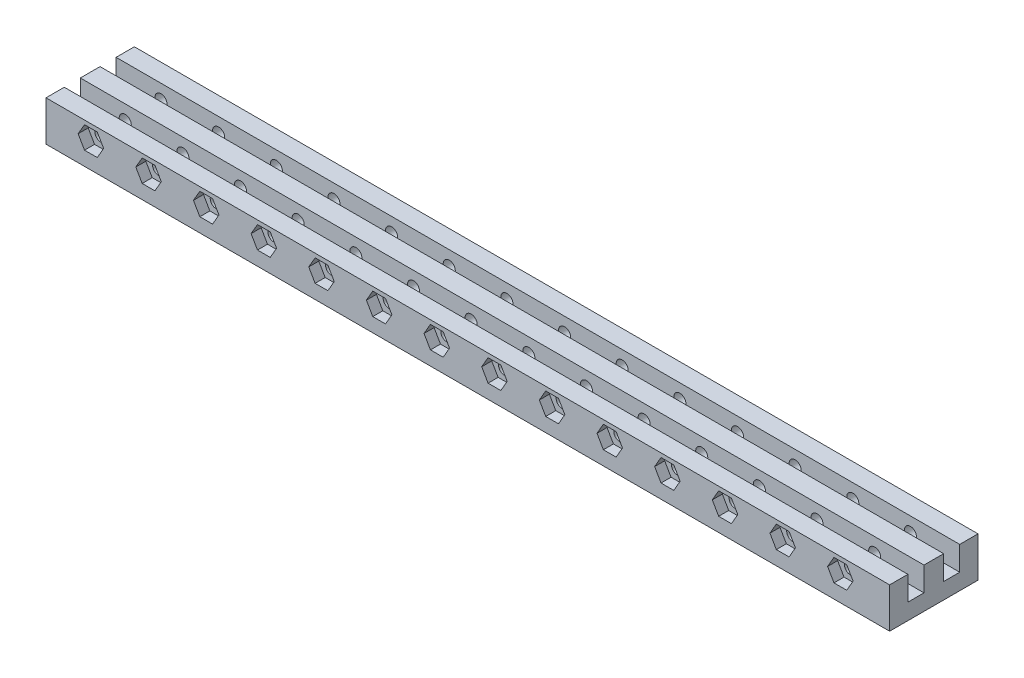
SolidWorks part; units mm, degrees
ref_plane "Front Plane" through (0, 0, 0) normal (0, 0, 1) x (1, 0, 0)
ref_plane "Top Plane" through (0, 0, 0) normal (0, 1, 0) x (1, 0, 0)
ref_plane "Right Plane" through (0, 0, 0) normal (1, 0, 0) x (0, 0, -1)
sketch "Sketch1" plane through (0, 0, 0) normal (0, 1, 0) x (1, 0, 0)
  line L1 (105, -11) -> (-105, -11)
  line L2 (105, -11) -> (105, 11)
  line L3 (105, 11) -> (-105, 11)
  line L4 (-105, -11) -> (-105, 11)
  line L5 (0, 11) -> (0, -11) construction
  line L6 (105, 0) -> (-105, 0) construction
  point P0 (0, 0)
  point P4 (0, 0)
  dimension "D1" = 210
  dimension "D2" = 22
extrude "Boss-Extrude1" add sketch "Sketch1" along normal blind 10
sketch "Sketch2" plane through (0, 10, 0) normal (0, 1, 0) x (1, 0, 0)
  line L0 (-105, 11) -> (-105, -11) construction
  line L1 (-105, -2.4504) -> (105, -2.4504)
  line L2 (-105, -2.4504) -> (-105, -6.4504)
  line L3 (-105, -6.4504) -> (105, -6.4504)
  line L4 (105, -2.4504) -> (105, -6.4504)
  line L5 (105, -11) -> (105, 11) construction
  line L6 (-105, 0) -> (108.3852, 0) construction
  line L7 (-105, -11) -> (105, -11) construction
  line L8 (105, 2.4504) -> (105, 6.4504)
  line L9 (-105, 2.4504) -> (-105, 6.4504)
  line L10 (-105, 2.4504) -> (105, 2.4504)
  line L11 (-105, 6.4504) -> (105, 6.4504)
  dimension "D1" = 4
extrude "Cut-Extrude1" cut sketch "Sketch2" against normal blind 6
sketch "Sketch3" plane through (0, 0, 11) normal (0, 0, 1) x (1, 0, 0)
  line L6 (-97, 6.25) -> (-90.6491, 6.25) construction
  line L7 (-105, 10) -> (105, 10) construction
  line L8 (-90.6491, 6.25) -> (-92.2369, 9)
  line L9 (-92.2369, 9) -> (-95.4123, 9)
  line L10 (-95.4123, 9) -> (-97, 6.25)
  line L11 (-97, 6.25) -> (-95.4123, 3.5)
  line L12 (-95.4123, 3.5) -> (-92.2369, 3.5)
  line L13 (-92.2369, 3.5) -> (-90.6491, 6.25)
  line L14 (-105, 10) -> (-105, 0) construction
  line L15 (-86.6491, 10) -> (-86.6491, 0) construction
  line L16 (-105, 0) -> (105, 0) construction
  line L17 (-82.6491, 6.25) -> (-81.0614, 9)
  line L18 (-81.0614, 3.5) -> (-82.6491, 6.25)
  line L19 (-77.886, 3.5) -> (-81.0614, 3.5)
  line L20 (-76.2983, 6.25) -> (-77.886, 3.5)
  line L21 (-77.886, 9) -> (-76.2983, 6.25)
  line L22 (-81.0614, 9) -> (-77.886, 9)
  line L23 (-72.2983, 10) -> (-72.2983, 0) construction
  line L24 (-57.9474, 10) -> (-57.9474, 0) construction
  line L25 (-47.5966, 6.25) -> (-53.9474, 6.25) construction
  line L26 (-63.5352, 9) -> (-66.7106, 9)
  line L27 (-66.7106, 9) -> (-68.2983, 6.25)
  line L28 (-68.2983, 6.25) -> (-66.7106, 3.5)
  line L29 (-66.7106, 3.5) -> (-63.5352, 3.5)
  line L30 (-63.5352, 3.5) -> (-61.9474, 6.25)
  line L31 (-61.9474, 6.25) -> (-63.5352, 9)
  line L32 (-52.3597, 3.5) -> (-53.9474, 6.25)
  line L33 (-49.1843, 3.5) -> (-52.3597, 3.5)
  line L34 (-47.5966, 6.25) -> (-49.1843, 3.5)
  line L35 (-49.1843, 9) -> (-47.5966, 6.25)
  line L36 (-52.3597, 9) -> (-49.1843, 9)
  line L37 (-53.9474, 6.25) -> (-52.3597, 9)
  line L38 (-68.2983, 6.25) -> (-61.9474, 6.25) construction
  line L39 (-18.8949, 6.25) -> (-25.2457, 6.25) construction
  line L52 (-34.8334, 9) -> (-38.0089, 9)
  line L53 (-38.0089, 9) -> (-39.5966, 6.25)
  line L54 (-39.5966, 6.25) -> (-38.0089, 3.5)
  line L55 (-38.0089, 3.5) -> (-34.8334, 3.5)
  line L56 (-34.8334, 3.5) -> (-33.2457, 6.25)
  line L57 (-33.2457, 6.25) -> (-34.8334, 9)
  line L58 (-23.658, 3.5) -> (-25.2457, 6.25)
  line L59 (-20.4826, 3.5) -> (-23.658, 3.5)
  line L60 (-18.8949, 6.25) -> (-20.4826, 3.5)
  line L61 (-20.4826, 9) -> (-18.8949, 6.25)
  line L62 (-23.658, 9) -> (-20.4826, 9)
  line L63 (-25.2457, 6.25) -> (-23.658, 9)
  line L64 (-14.8949, 10) -> (-14.8949, 0) construction
  line L65 (-10.8949, 6.25) -> (-4.544, 6.25) construction
  line L66 (38.5085, 6.25) -> (32.1577, 6.25) construction
  line L67 (17.8068, 6.25) -> (24.1577, 6.25) construction
  line L68 (28.1577, 10) -> (28.1577, 0) construction
  line L69 (42.5085, 10) -> (42.5085, 0) construction
  line L70 (56.8594, 10) -> (56.8594, 0) construction
  line L71 (67.2102, 6.25) -> (60.8594, 6.25) construction
  line L72 (-4.544, 6.25) -> (-6.1317, 9)
  line L73 (-6.1317, 9) -> (-9.3072, 9)
  line L74 (-9.3072, 9) -> (-10.8949, 6.25)
  line L75 (-10.8949, 6.25) -> (-9.3072, 3.5)
  line L76 (-9.3072, 3.5) -> (-6.1317, 3.5)
  line L77 (-6.1317, 3.5) -> (-4.544, 6.25)
  line L78 (3.456, 6.25) -> (5.0437, 9)
  line L79 (5.0437, 3.5) -> (3.456, 6.25)
  line L80 (8.2191, 3.5) -> (5.0437, 3.5)
  line L81 (9.8068, 6.25) -> (8.2191, 3.5)
  line L82 (8.2191, 9) -> (9.8068, 6.25)
  line L83 (5.0437, 9) -> (8.2191, 9)
  line L84 (22.57, 9) -> (19.3945, 9)
  line L85 (19.3945, 9) -> (17.8068, 6.25)
  line L86 (17.8068, 6.25) -> (19.3945, 3.5)
  line L87 (19.3945, 3.5) -> (22.57, 3.5)
  line L88 (22.57, 3.5) -> (24.1577, 6.25)
  line L89 (24.1577, 6.25) -> (22.57, 9)
  line L90 (33.7454, 3.5) -> (32.1577, 6.25)
  line L91 (36.9208, 3.5) -> (33.7454, 3.5)
  line L92 (38.5085, 6.25) -> (36.9208, 3.5)
  line L93 (36.9208, 9) -> (38.5085, 6.25)
  line L94 (33.7454, 9) -> (36.9208, 9)
  line L95 (32.1577, 6.25) -> (33.7454, 9)
  line L108 (51.2717, 9) -> (48.0962, 9)
  line L109 (48.0962, 9) -> (46.5085, 6.25)
  line L110 (46.5085, 6.25) -> (48.0962, 3.5)
  line L111 (48.0962, 3.5) -> (51.2717, 3.5)
  line L112 (51.2717, 3.5) -> (52.8594, 6.25)
  line L113 (52.8594, 6.25) -> (51.2717, 9)
  line L114 (62.4471, 3.5) -> (60.8594, 6.25)
  line L115 (65.6225, 3.5) -> (62.4471, 3.5)
  line L116 (67.2102, 6.25) -> (65.6225, 3.5)
  line L117 (65.6225, 9) -> (67.2102, 6.25)
  line L118 (62.4471, 9) -> (65.6225, 9)
  line L119 (60.8594, 6.25) -> (62.4471, 9)
  line L120 (71.2102, 10) -> (71.2102, 0) construction
  line L121 (75.2102, 6.25) -> (81.5611, 6.25) construction
  line L122 (85.5611, 10) -> (85.5611, 0) construction
  line L123 (81.5611, 6.25) -> (79.9734, 9)
  line L124 (79.9734, 9) -> (76.7979, 9)
  line L125 (76.7979, 9) -> (75.2102, 6.25)
  line L126 (75.2102, 6.25) -> (76.7979, 3.5)
  line L127 (76.7979, 3.5) -> (79.9734, 3.5)
  line L128 (79.9734, 3.5) -> (81.5611, 6.25)
  line L129 (89.5611, 6.25) -> (91.1488, 9)
  line L130 (91.1488, 3.5) -> (89.5611, 6.25)
  line L131 (94.3242, 3.5) -> (91.1488, 3.5)
  line L132 (95.9119, 6.25) -> (94.3242, 3.5)
  line L133 (94.3242, 9) -> (95.9119, 6.25)
  line L134 (91.1488, 9) -> (94.3242, 9)
  circle A0 centre (-93.8246, 6.25) radius 2.75 construction
  circle A1 centre (-50.772, 6.25) radius 2.75 construction
  circle A2 centre (-65.1229, 6.25) radius 2.75 construction
  circle A3 centre (-22.0703, 6.25) radius 2.75 construction
  circle A4 centre (-7.7195, 6.25) radius 2.75 construction
  circle A5 centre (35.3331, 6.25) radius 2.75 construction
  circle A6 centre (20.9823, 6.25) radius 2.75 construction
  circle A7 centre (64.0348, 6.25) radius 2.75 construction
  circle A8 centre (78.3857, 6.25) radius 2.75 construction
  dimension "D1" = 5.5
  dimension "D2" = 6.3509
  dimension "D3" = 1
  dimension "D4" = 8
  dimension "D5" = 4
  dimension "D6" = 4
  dimension "D7" = 4
  dimension "D8" = 4
extrude "Cut-Extrude3" cut sketch "Sketch3" against normal blind 2.5
sketch "Sketch8" plane through (0, 0, 11) normal (0, 0, 1) x (1, 0, 0)
  line L0 (-97, 6.25) -> (-90.6491, 6.25) construction
  line L2 (-93.8246, 9) -> (-93.8246, 3.5) construction
  line L3 (-92.2369, 9) -> (-95.4123, 9) construction
  line L4 (-95.4123, 3.5) -> (-92.2369, 3.5) construction
sketch "Sketch9" plane through (0, 0, 11) normal (0, 0, 1) x (1, 0, 0)
  line L0 (-97, 6.25) -> (-90.6491, 6.25) construction
  line L1 (-79.4737, 9) -> (-79.4737, 3.5) construction
  line L2 (-77.886, 9) -> (-81.0614, 9) construction
  line L3 (-81.0614, 3.5) -> (-77.886, 3.5) construction
  line L4 (-93.8246, 9) -> (-93.8246, 3.5) construction
  line L5 (-93.8246, 6.25) -> (-79.4737, 6.25) construction
  circle A0 centre (-93.8246, 6.25) radius 1.5
  circle A1 centre (-79.4737, 6.25) radius 1.5
  circle A2 centre (-65.1229, 6.25) radius 1.5
  circle A3 centre (-50.772, 6.25) radius 1.5
  circle A4 centre (-36.4212, 6.25) radius 1.5
  circle A5 centre (-22.0703, 6.25) radius 1.5
  circle A6 centre (-7.7195, 6.25) radius 1.5
  circle A7 centre (6.6314, 6.25) radius 1.5
  circle A8 centre (20.9823, 6.25) radius 1.5
  circle A9 centre (35.3331, 6.25) radius 1.5
  circle A10 centre (49.684, 6.25) radius 1.5
  circle A11 centre (64.0348, 6.25) radius 1.5
  circle A12 centre (78.3857, 6.25) radius 1.5
  circle A13 centre (92.7365, 6.25) radius 1.5
  dimension "D1" = 14.3509
  dimension "D3" = 14.3509
  dimension "D2" = 14
extrude "Cut-Extrude4" cut sketch "Sketch9" against normal through all
